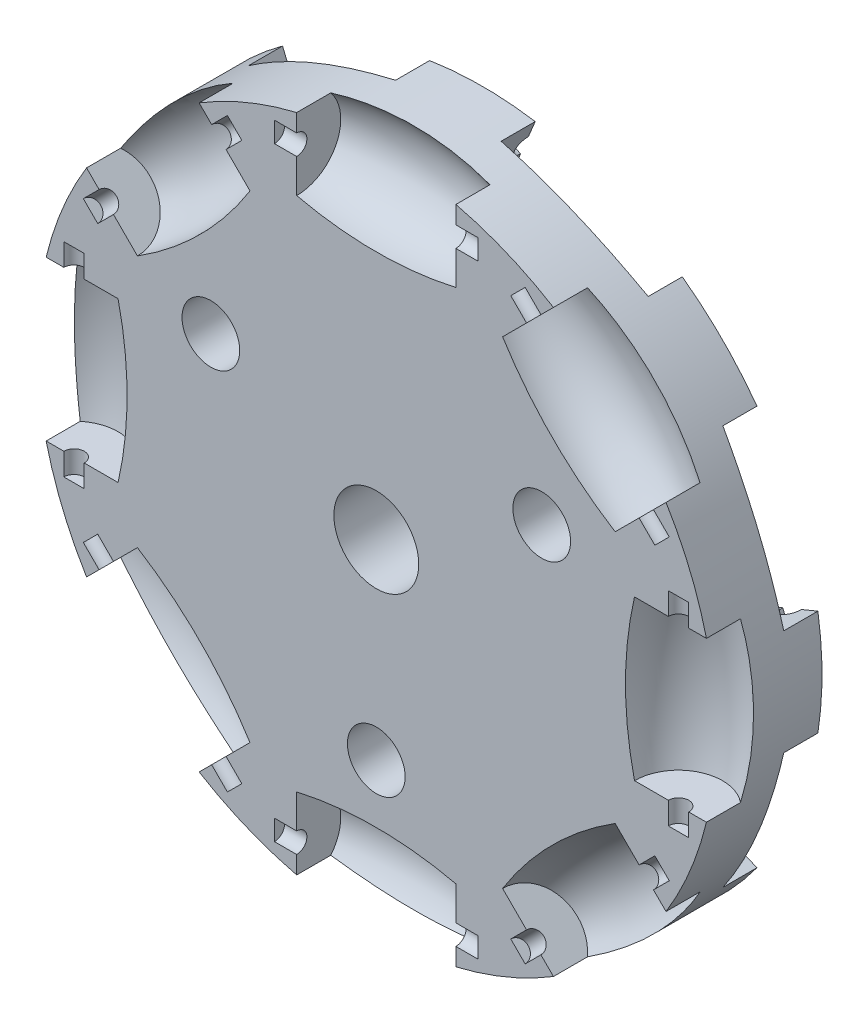
SolidWorks part; units mm, degrees
ref_plane "Front Plane" through (0, 0, 0) normal (0, 0, 1) x (1, 0, 0)
ref_plane "Top Plane" through (0, 0, 0) normal (0, 1, 0) x (1, 0, 0)
ref_plane "Right Plane" through (0, 0, 0) normal (1, 0, 0) x (0, 0, -1)
sketch "Sketch1" plane through (0, 0, 0) normal (0, 0, 1) x (1, 0, 0)
  circle A0 centre (0, 0) radius 25.4
  point P11 (0, 0)
  dimension "D1" = 50.8
extrude "Boss-Extrude1" add sketch "Sketch1" along normal mid plane 7.9375
ref_plane "Plane1" through (0, 0, 3.9688) normal (0, 0, 1) x (1, 0, 0)
ref_plane "Plane2" through (0, 0, -3.9688) normal (0, 0, 1) x (1, 0, 0)
sketch "Sketch5" plane through (0, 0, 3.9688) normal (0, 0, 1) x (1, 0, 0)
  line L0 (-5.9531, 25.8994) -> (-5.9531, 22.606)
  line L1 (-5.9531, 22.606) -> (5.9531, 22.606)
  line L2 (5.9531, 22.606) -> (5.9531, 25.8994)
  line L3 (-5.9531, 22.606) -> (-8.0326, 22.606) construction
  arc A2 (-5.9531, 25.8994) -> (5.9531, 25.8994) centre (0, 0) cw
  point P2 (0, 26.5748)
  point P7 (0, 22.606)
  dimension "D1" = 11.9062
  dimension "D2" = 7.9375
  dimension "D3" = 22.606
revolve "Cut-Revolve5" cut sketch "Sketch5" angle 360 about L1
sketch "Sketch8" plane through (0, 0, -3.9688) normal (0, 0, 1) x (1, 0, 0)
  line L0 (4.4113, 26.2061) -> (3.151, 23.1634)
  line L1 (3.151, 23.1634) -> (14.1509, 18.6071)
  line L2 (14.1509, 18.6071) -> (15.4112, 21.6497)
  line L3 (3.151, 23.1634) -> (-2.0499, 25.3177) construction
  line L4 (0, 0) -> (9.7202, 23.4665) construction
  line L5 (0, 0) -> (0, 7.8748) construction
  arc A0 (4.4113, 26.2061) -> (15.4112, 21.6497) centre (0, 0) cw
  arc A2 (-5.9531, 24.6925) -> (5.9531, 24.6925) centre (0, 0) ccw construction
  point P6 (8.6509, 20.8852)
  point P14 (10.1697, 24.5519)
  dimension "D1" = 11.9062
  dimension "D2" = 7.9375
  dimension "D3" = 22.5
  dimension "D4" = 22.606
revolve "Cut-Revolve6" cut sketch "Sketch8" angle 360 about L3
sketch "Sketch6" plane through (0, 0, 0) normal (1, 0, 0) x (0, 0, -1)
  arc A0 (-3.9688, 19.3126) -> (-1.4207, 24.6925) centre (-3.9688, 22.606) ccw construction
  circle A1 centre (-3.9688, 22.606) radius 0.762
  point P4 (-3.9688, 22.606)
  dimension "D1" = 1.524
extrude "Cut-Extrude2" cut sketch "Sketch6" against normal mid plane 15.24
ref_axis "Axis1" through (0, 0, -8.8615) along (0, 0, 1)
ref_plane "Plane3" through (0, 0, 0) normal (0.9239, -0.3827, 0) x (0, 0, -1)
sketch "Sketch10" plane through (0, 0, 0) normal (0.9239, -0.3827, 0) x (0, 0, -1)
  arc A1 (1.4207, 24.6925) -> (3.9688, 19.3126) centre (3.9688, 22.606) ccw construction
  circle A2 centre (3.9688, 22.606) radius 0.762
  point P4 (3.9688, 22.606)
  dimension "D1" = 1.524
extrude "Cut-Extrude3" cut sketch "Sketch10" against normal mid plane 15.24
pattern_circular "CirPattern1" count 8 over 360 about axis through (0, 0, 3.9688) along (0, 0, -1) of "Cut-Revolve5", "Cut-Revolve6", "Cut-Extrude2", "Cut-Extrude3"
sketch "Sketch16" plane through (0, 0, 3.9688) normal (0, 0, 1) x (1, 0, 0)
  circle A0 centre (0, -14.2875) radius 2.159
  circle A1 centre (-12.3733, 7.1437) radius 2.159
  circle A2 centre (12.3733, 7.1438) radius 2.159
  point P9 (0, 0)
  dimension "D1" = 4.318
  dimension "D2" = 14.2875
  dimension "D3" = 3
extrude "Cut-Extrude7" cut sketch "Sketch16" against normal through all
sketch "Sketch17" plane through (0, 0, 3.9688) normal (0, 0, 1) x (1, 0, 0)
  circle A0 centre (0, 0) radius 3.175
  dimension "D1" = 6.35
extrude "Cut-Extrude8" cut sketch "Sketch17" against normal through all
